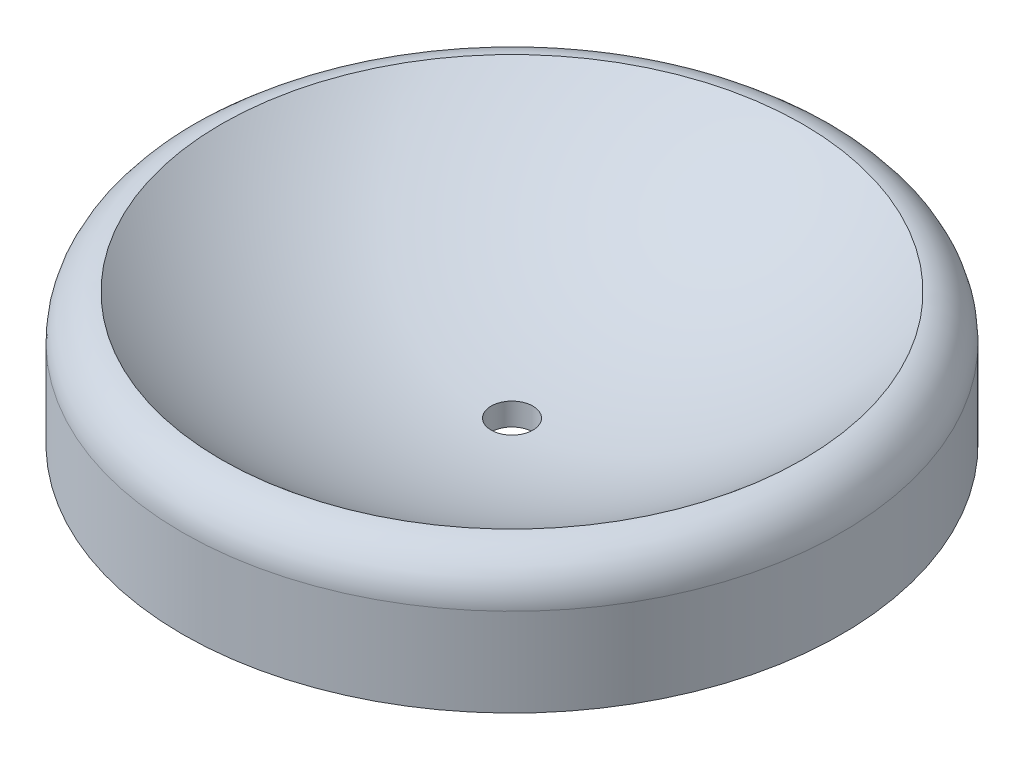
SolidWorks part; units mm, degrees
ref_plane "Front Plane" through (0, 0, 0) normal (0, 0, 1) x (1, 0, 0)
ref_plane "Top Plane" through (0, 0, 0) normal (0, 1, 0) x (1, 0, 0)
ref_plane "Right Plane" through (0, 0, 0) normal (1, 0, 0) x (0, 0, -1)
sketch "Sketch1" plane through (0, 0, 0) normal (0, 1, 0) x (1, 0, 0)
  circle A0 centre (0, 0) radius 15
  dimension "D1" = 30
extrude "Boss-Extrude1" add sketch "Sketch1" along normal blind 6
sketch "Sketch2" plane through (0, 6, 0) normal (0, 1, 0) x (1, 0, 0)
  circle A0 centre (0, 0) radius 0.95
  dimension "D1" = 1.9
extrude "Cut-Extrude1" cut sketch "Sketch2" against normal blind 8 and the other way blind 10
sketch "Sketch4" plane through (0, 0, 0) normal (1, 0, 0) x (0, 0, -1)
  line L0 (-20, 21) -> (20, 21)
  line L1 (-15, 0) -> (15, 0) construction
  arc A0 (-20, 21) -> (20, 21) centre (0, 21) ccw
  dimension "D1" = 40
  dimension "D2" = 21
revolve "Cut-Revolve6" cut sketch "Sketch4" angle 360 about L0
fillet "Fillet1" radius 2 1 edges at (0, 6, 15)
